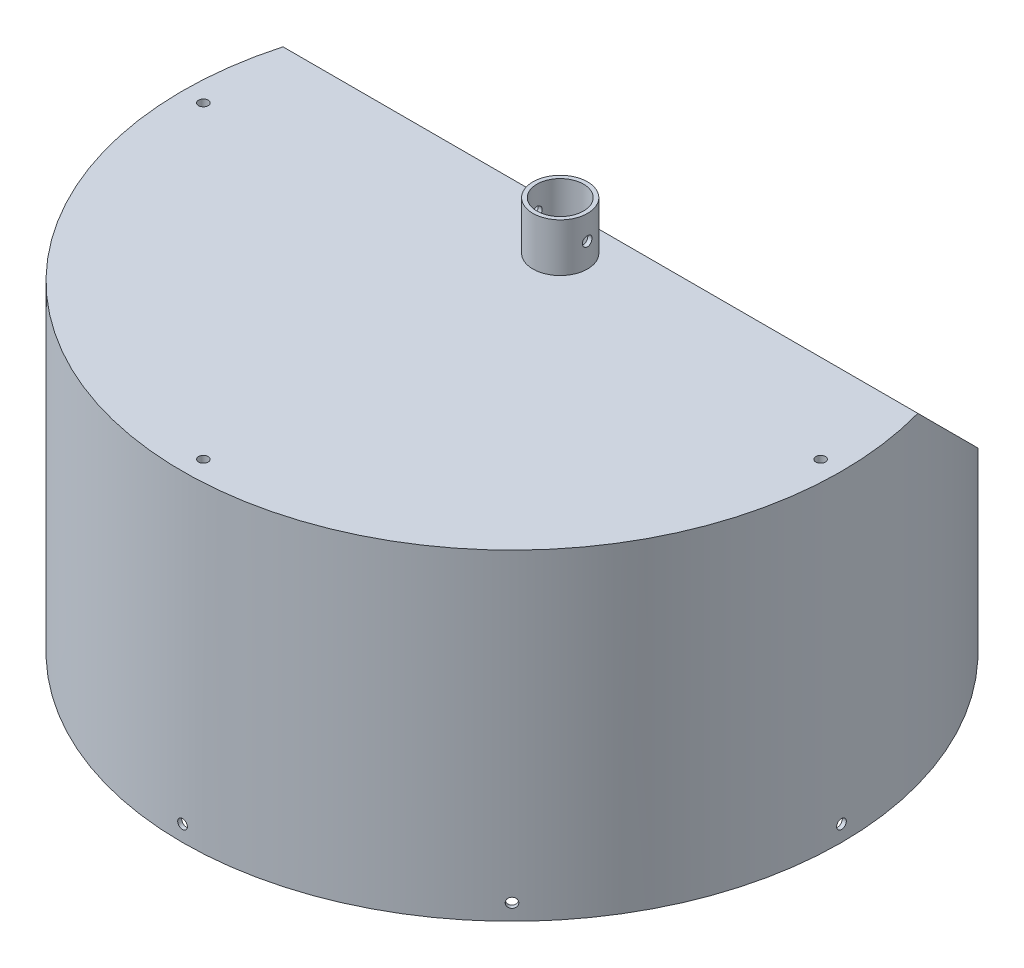
SolidWorks part; units mm, degrees
material "PLA"
ref_plane "Front Plane" through (0, 0, 0) normal (0, 0, 1) x (1, 0, 0)
ref_plane "Top Plane" through (0, 0, 0) normal (0, 1, 0) x (1, 0, 0)
ref_plane "Right Plane" through (0, 0, 0) normal (1, 0, 0) x (0, 0, -1)
sketch "Sketch1" plane through (0, 0, 0) normal (0, 1, 0) x (1, 0, 0)
  circle A0 centre (0, 0) radius 205
  dimension "D1" = 410
extrude "Boss-Extrude1" add sketch "Sketch1" along normal blind 900
sketch "Sketch2" plane through (0, 0, 0) normal (1, 0, 0) x (0, 0, -1)
  line L0 (55, 900) -> (205, 750)
  line L1 (-205, 0) -> (205, 0) construction
  line L2 (-205, 0) -> (-205, 900) construction
  line L3 (-205, 900) -> (205, 900) construction
  line L4 (205, 0) -> (205, 900) construction
  line L5 (205, 750) -> (205, 900)
  line L6 (205, 900) -> (55, 900)
  dimension "D1" = 150
extrude "Cut-Extrude1" cut sketch "Sketch2" against normal through all both and the other way through all
sketch "Sketch9" plane through (0, 900, 0) normal (0, 1, 0) x (1, 0, 0)
  line L0 (-202.793, 30) -> (202.793, 30) construction
  line L1 (-197.4842, 55) -> (197.4842, 55) construction
  arc A0 (-197.4842, 55) -> (197.4842, 55) centre (0, 0) ccw construction
  circle A1 centre (0, 30) radius 17
  circle A2 centre (0, 30) radius 14.5
  dimension "D2" = 34
  dimension "D3" = 29
  dimension "D1" = 25
extrude "Boss-Extrude3" add sketch "Sketch9" along normal blind 30
sketch "Sketch32" plane through (0, 477.5, -477.5) normal (0, 0.7071, -0.7071) x (1, 0, 0)
  line L0 (-197.4842, -597.5052) -> (197.4842, -597.5052) construction
  line L1 (77.5, -582.5052) -> (-77.5, -582.5052)
  line L2 (87.5, -572.5052) -> (87.5, -457.5052)
  line L3 (77.5, -447.5052) -> (-77.5, -447.5052)
  line L4 (-87.5, -572.5052) -> (-87.5, -457.5052)
  line L5 (87.5, -582.5052) -> (-87.5, -447.5052) construction
  line L6 (87.5, -447.5052) -> (-87.5, -582.5052) construction
  line L7 (0, -597.5052) -> (0, -385.3732) construction
  arc A0 (-87.5, -457.5052) -> (-77.5, -447.5052) centre (-77.5, -457.5052) cw
  arc A1 (-87.5, -572.5052) -> (-77.5, -582.5052) centre (-77.5, -572.5052) ccw
  arc A2 (77.5, -582.5052) -> (87.5, -572.5052) centre (77.5, -572.5052) ccw
  arc A3 (87.5, -457.5052) -> (77.5, -447.5052) centre (77.5, -457.5052) ccw
  ellipse E0 centre (0, -675.287) end of major axis (0, -385.3732) minor radius 205 (197.4842, -597.5052) -> (-197.4842, -597.5052) ccw construction
  point P0 (0, -515.0052)
  dimension "D5" = 10
  dimension "D1" = 175
  dimension "D2" = 135
  dimension "D3" = 15
  dimension "D4" = 87.5
extrude "Cut-Extrude26" cut sketch "Sketch32" against normal blind 12
sketch "Sketch38" plane through (-87.5, 0, 0) normal (1, 0, 0) x (0, 0, -1)
  line L0 (80.1023, 857.9271) -> (129.5998, 808.4297)
  line L1 (80.1023, 857.9271) -> (86.4663, 864.2911)
  line L2 (129.5998, 808.4297) -> (135.9637, 814.7936)
  line L3 (86.4663, 864.2911) -> (135.9637, 814.7936)
  line L4 (145.5097, 792.5198) -> (64.1924, 873.837) construction
  line L5 (64.1924, 873.837) -> (72.6777, 882.3223) construction
  line L10 (153.9949, 801.0051) -> (72.6777, 882.3223) construction
  point P10 (104.851, 833.1784)
  dimension "D1" = 57.5
  dimension "D2" = 70
  dimension "D3" = 3
extrude "Cut-Extrude34" cut sketch "Sketch38" against normal blind 5 and the other way blind 180
shell "Shell1" thickness 5 removed face at (0, 0, 205)
sketch "Sketch40" plane through (0, 900, 0) normal (0, 1, 0) x (1, 0, 0)
  circle A1 centre (0, 30) radius 14.5
  circle A2 centre (0, 30) radius 14.5
  dimension "D1" = 0
extrude "Cut-Extrude36" cut sketch "Sketch40" against normal blind 10
sketch "Sketch41" plane through (92.5, 0, 0) normal (-1, 0, 0) x (0, 0, 1)
  line L4 (-80.1023, 857.9271) -> (-86.4663, 864.2911)
  line L5 (-86.4663, 864.2911) -> (-135.9637, 814.7936)
  line L6 (-135.9637, 814.7936) -> (-129.5998, 808.4297)
  line L7 (-129.5998, 808.4297) -> (-80.1023, 857.9271)
  line L8 (-80.1023, 857.9271) -> (-86.4663, 864.2911)
  line L9 (-86.4663, 864.2911) -> (-135.9637, 814.7936)
  line L10 (-135.9637, 814.7936) -> (-129.5998, 808.4297)
  line L11 (-129.5998, 808.4297) -> (-80.1023, 857.9271)
  dimension "D1" = 0
extrude "Cut-Extrude37" cut sketch "Sketch41" against normal blind 20 and the other way blind 210
ref_plane "Plane1" through (0, 700, 0) normal (0, 1, 0) x (1, 0, 0)
sketch "Sketch42" plane through (0, 700, 0) normal (0, 1, 0) x (1, 0, 0)
  circle A0 centre (0, 0) radius 205
  dimension "D1" = 410
extrude "Cut-Extrude38" cut sketch "Sketch42" against normal blind 710
sketch "Sketch43" plane through (0, 900, 0) normal (0, 1, 0) x (1, 0, 0)
  line L0 (-205, 0) -> (205, 0) construction
  line L1 (0, -205) -> (0, 55) construction
  line L2 (-197.4842, 55) -> (197.4842, 55) construction
  arc A0 (-197.4842, 55) -> (197.4842, 55) centre (0, 0) ccw construction
  circle A1 centre (-192, 0) radius 3
  circle A2 centre (192, 0) radius 3
  circle A3 centre (0, -192) radius 3
  dimension "D1" = 6
  dimension "D2" = 384
  dimension "D3" = 192
  dimension "D4" = 192
extrude "Cut-Extrude39" cut sketch "Sketch43" against normal through all
sketch "Sketch44" plane through (0, 0, 0) normal (1, 0, 0) x (0, 0, -1)
  line L0 (30, 930) -> (30, 900) construction
  line L1 (47, 930) -> (13, 930) construction
  line L2 (55, 900) -> (-205, 900) construction
  circle A0 centre (30, 915) radius 3
  dimension "D1" = 6
extrude "Cut-Extrude40" cut sketch "Sketch44" against normal through all both and the other way through all
sketch "Sketch45" plane through (0, 700, 0) normal (0, -1, 0) x (1, 0, 0)
  circle A0 centre (0, 0) radius 200 construction
  circle A1 centre (0, 0) radius 200
  circle A2 centre (0, 0) radius 202.5
  dimension "D1" = 2.5
extrude "Cut-Extrude41" cut sketch "Sketch45" against normal blind 20
sketch "Sketch46" plane through (0, 0, 0) normal (0, 0, 1) x (1, 0, 0)
  line L0 (0, 680.818) -> (0, 944.8041) construction
  line L1 (-205, 700) -> (205, 700) construction
  circle A0 centre (0, 710) radius 3
  dimension "D1" = 6
  dimension "D2" = 10
extrude "Cut-Extrude42" cut sketch "Sketch46" against normal through all both and the other way through all
sketch "Sketch48" plane through (0, 0, 0) normal (0, 0, 1) x (1, 0, 0)
  line L0 (0, 989.2703) -> (0, 689.2703) construction
  dimension "D1" = 300
pattern_circular "CirPattern1" count 4 every 45 about axis through (0, 989.2703, 0) along (0, -1, 0) of "Cut-Extrude42"
sketch "Sketch49" plane through (0, 469.0147, -469.0147) normal (0, 0.7071, -0.7071) x (1, 0, 0)
  line L1 (39.5, -512.5052) -> (55.5, -512.5052)
  line L2 (37.5, -514.5052) -> (37.5, -530.5052)
  line L3 (39.5, -532.5052) -> (55.5, -532.5052)
  line L4 (57.5, -514.5052) -> (57.5, -530.5052)
  line L5 (37.5, -512.5052) -> (57.5, -532.5052) construction
  line L6 (37.5, -532.5052) -> (57.5, -512.5052) construction
  line L10 (87.5, -572.5052) -> (87.5, -457.5052) construction
  line L11 (-77.5, -582.5052) -> (77.5, -582.5052) construction
  line L12 (0, -447.5052) -> (0, -582.5052) construction
  line L13 (77.5, -447.5052) -> (-77.5, -447.5052) construction
  line L14 (-77.5, -582.5052) -> (77.5, -582.5052) construction
  line L15 (-39.5, -512.5052) -> (-55.5, -512.5052)
  line L16 (-37.5, -532.5052) -> (-57.5, -512.5052) construction
  line L17 (-37.5, -512.5052) -> (-57.5, -532.5052) construction
  line L18 (-57.5, -514.5052) -> (-57.5, -530.5052)
  line L19 (-39.5, -532.5052) -> (-55.5, -532.5052)
  line L20 (-37.5, -514.5052) -> (-37.5, -530.5052)
  arc A0 (37.5, -530.5052) -> (39.5, -532.5052) centre (39.5, -530.5052) ccw
  arc A1 (55.5, -532.5052) -> (57.5, -530.5052) centre (55.5, -530.5052) ccw
  arc A2 (57.5, -514.5052) -> (55.5, -512.5052) centre (55.5, -514.5052) ccw
  arc A3 (39.5, -512.5052) -> (37.5, -514.5052) centre (39.5, -514.5052) ccw
  arc A4 (-39.5, -512.5052) -> (-37.5, -514.5052) centre (-39.5, -514.5052) cw
  arc A5 (-57.5, -514.5052) -> (-55.5, -512.5052) centre (-55.5, -514.5052) cw
  arc A6 (-55.5, -532.5052) -> (-57.5, -530.5052) centre (-55.5, -530.5052) cw
  arc A7 (-37.5, -530.5052) -> (-39.5, -532.5052) centre (-39.5, -530.5052) cw
  point P0 (47.5, -522.5052)
  point P43 (-47.5, -522.5052)
  dimension "D5" = 2
  dimension "D1" = 20
  dimension "D2" = 20
  dimension "D3" = 30
  dimension "D4" = 50
extrude "Cut-Extrude43" cut sketch "Sketch49" against normal blind 20
